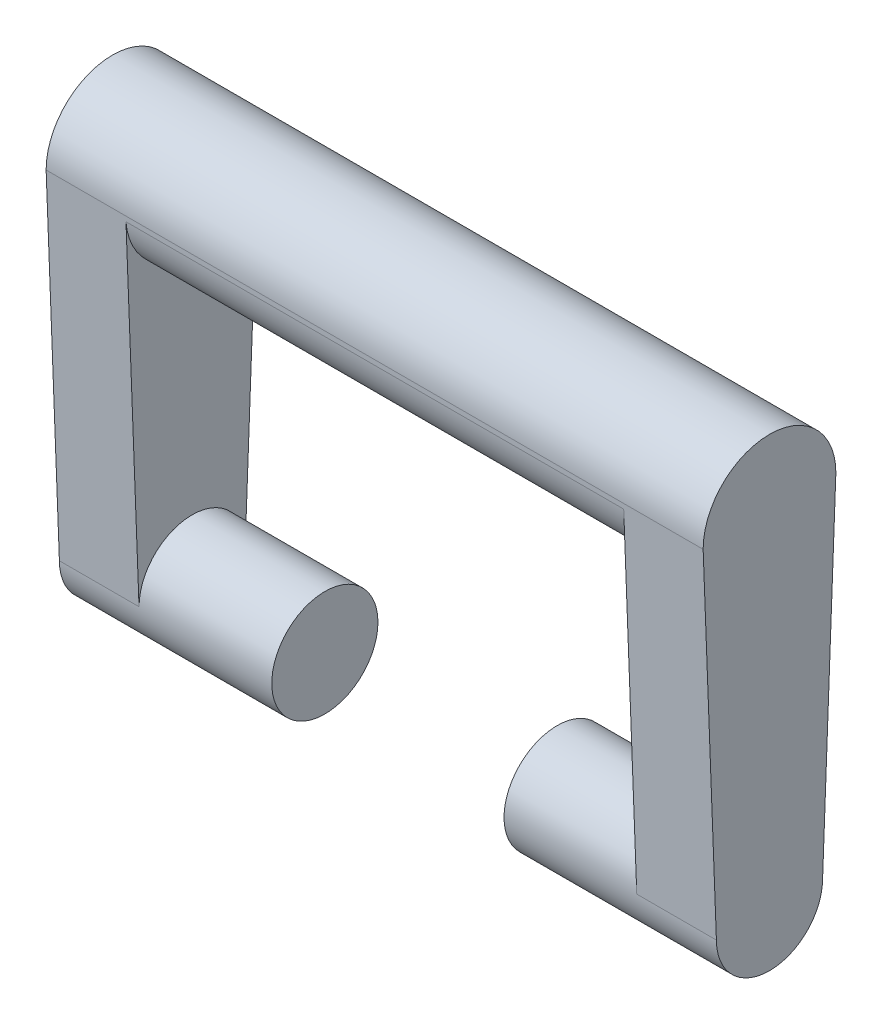
SolidWorks part; units mm, degrees
note: The reader was unsure of these and kept them because the rebuilt part matched: shared geometry of "Sketch2<9>", "Sketch2<11>".
ref_plane "Front Plane" through (0, 0, 0) normal (0, 0, 1) x (1, 0, 0)
ref_plane "Top Plane" through (0, 0, 0) normal (0, 1, 0) x (1, 0, 0)
ref_plane "Right Plane" through (0, 0, 0) normal (1, 0, 0) x (0, 0, -1)
sketch "Sketch2" plane through (0, 0, 0) normal (1, 0, 0) x (0, 0, -1)
  line L0 (0, 44.45) -> (0, -44.45) construction
  line L1 (12.7, -44.45) -> (-12.7, -44.45)
  line L2 (12.7, -44.45) -> (12.7, 44.45)
  line L3 (12.7, 44.45) -> (-12.7, 44.45)
  line L4 (-12.7, -44.45) -> (-12.7, 44.45)
  line L5 (12.7, -44.45) -> (-12.7, 44.45) construction
  line L6 (12.7, 44.45) -> (-12.7, -44.45) construction
  line L7 (-12.7, 31.75) -> (-10.16, -34.29)
  line L8 (12.7, 31.75) -> (10.16, -34.29)
  line L9 (-12.7, 31.75) -> (12.7, 31.75) construction
  line L10 (-10.16, -34.29) -> (10.16, -34.29) construction
  circle A0 centre (0, 31.75) radius 12.7
  circle A1 centre (0, -34.29) radius 10.16
  point P0 (0, 0)
  dimension "D3" = 10.16
  dimension "D1" = 88.9
  dimension "D2" = 25.4
extrude "Boss-Extrude4" add sketch "Sketch2" along normal blind 15.24 contours A0 | A1 L2 A0 L4 | A1
extrude "Boss-Extrude5" add sketch "Sketch2<9>" along normal blind 62.865 contours A0
sketch "Sketch2<9>" plane through (0, 0, 0) normal (1, 0, 0) x (0, 0, -1) same geometry as "Sketch2"
extrude "Boss-Extrude6" add sketch "Sketch2<11>" along normal blind 40.64 contours A1
sketch "Sketch2<11>" plane through (0, 0, 0) normal (1, 0, 0) x (0, 0, -1) same geometry as "Sketch2"
ref_plane "Plane1" through (62.865, 0, 0) normal (1, 0, 0) x (0, 0, -1)
mirror "Mirror1" about plane through (62.865, 0, 0) normal (1, 0, 0) of bodies 105
